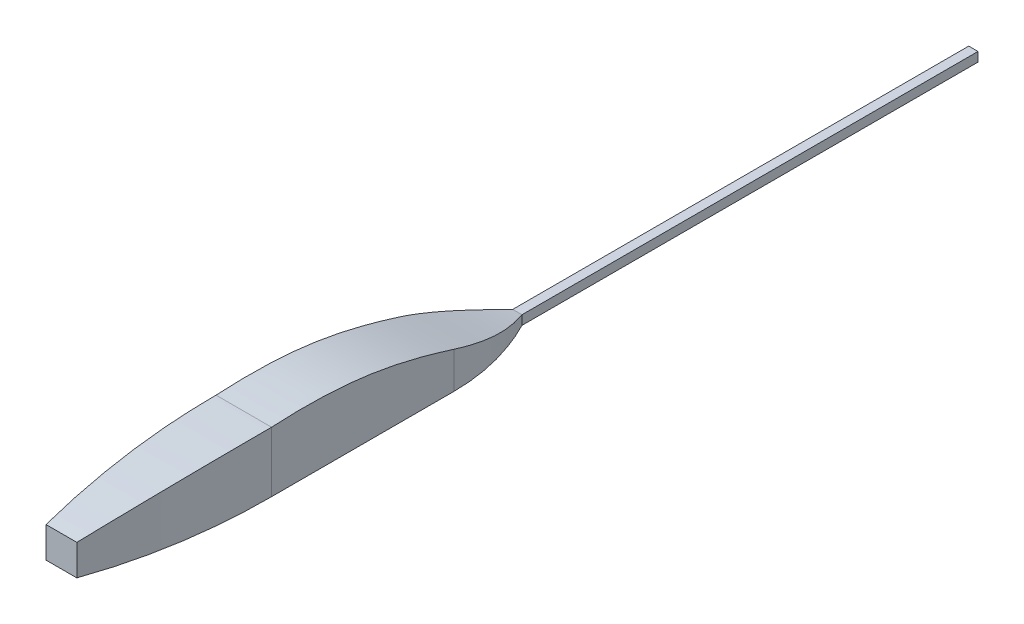
SolidWorks part; units mm, degrees
ref_plane "Front Plane" through (0, 0, 0) normal (0, 0, 1) x (1, 0, 0)
ref_plane "Top Plane" through (0, 0, 0) normal (0, 1, 0) x (1, 0, 0)
ref_plane "Right Plane" through (0, 0, 0) normal (1, 0, 0) x (0, 0, -1)
sketch "Sketch2" plane through (0, 0, 0) normal (0, 0, 1) x (1, 0, 0)
  line L0 (0, 0) -> (14.1421, 14.1421) construction
  line L1 (0, -35.75) -> (0, 35.75) construction
  line L2 (33, 0) -> (-33, 0) construction
  line L3 (-16.6421, 16.6421) -> (16.6421, 16.6421)
  line L4 (-14.1421, -14.1421) -> (14.1421, -14.1421)
  line L5 (-14.1421, -14.1421) -> (-14.1421, 14.1421)
  line L6 (-14.1421, 14.1421) -> (14.1421, 14.1421)
  line L7 (14.1421, -14.1421) -> (14.1421, 14.1421)
  line L8 (-14.1421, -14.1421) -> (14.1421, 14.1421) construction
  line L9 (-14.1421, 14.1421) -> (14.1421, -14.1421) construction
  line L10 (16.6421, -16.6421) -> (16.6421, 16.6421)
  line L11 (-16.6421, -16.6421) -> (16.6421, -16.6421)
  line L12 (-16.6421, -16.6421) -> (-16.6421, 16.6421)
  circle A1 centre (10.253, 10.253) radius 1.5
  circle A2 centre (-10.253, 10.253) radius 1.5
  circle A3 centre (-10.253, -10.253) radius 1.5
  circle A4 centre (10.253, -10.253) radius 1.5
  dimension "D2" = 3
  dimension "D1" = 20
  dimension "D3" = 4
  dimension "D4" = 2.5
sketch "YZ Extrude" plane through (0, 0, 0) normal (1, 0, 0) x (0, 0, -1)
  line L0 (0, 0) -> (197, 0) construction
  line L1 (197, 32.5) -> (197, -32.5) construction
  line L2 (197, 0) -> (394, 0) construction
  line L3 (0, -16.6421) -> (0, 16.6421) construction
  line L4 (394, -32.5) -> (985, -32.5)
  line L5 (98.5, 0) -> (98.5, 32.5)
  line L6 (0, 16.6421) -> (98.5, 32.5) construction
  line L7 (98.5, 32.5) -> (197, 32.5) construction
  line L8 (394, -32.5) -> (394, 32.5) construction
  line L10 (0, -16.6421) -> (98.5, -32.5) construction
  line L11 (98.5, -32.5) -> (197, -32.5) construction
  line L12 (197, -32.5) -> (394, -32.5)
  line L13 (985, -32.5) -> (985, -22.5)
  line L14 (492.5, -22.5) -> (985, -22.5)
  line L15 (492.5, -22.5) -> (492.5, 32.5) construction
  line L16 (297.0882, 29.5681) -> (345.6701, 20.5276)
  line L17 (345.6701, 20.5276) -> (393.2488, 7.178)
  line L19 (0, -16.6421) -> (0, 16.6421)
  line L20 (393.7193, 8.6942) -> (392.7782, 5.6619) construction
  spline S0 degree 2 poles (0, 16.6421) (98.5, 32.5) (197, 32.5) knots 0 0 0 1 1 1
  spline S1 degree 2 poles (0, -16.6421) (98.5, -32.5) (197, -32.5) knots 0 0 0 1 1 1
  spline S2 degree 3 poles (197, 32.5) (230.3593, 34.4809) (280.5151, 33.632) (379.8884, 14.8935) (442.9177, -10.7236) (492.5, -22.5) knots 0 0 0 0 0.331171 0.494445 1 1 1 1
  spline S3 degree 3 poles (393.1263, 7.216) (389.893, 8.2652) (383.442, 10.3586) (370.5028, 14.2229) (354.2993, 18.5842) (334.7723, 23.0541) (315.23, 26.8878) (295.637, 29.894) (276.0085, 32.1248) (259.5715, 32.9273) (246.4033, 32.6498) (236.4892, 31.9272) (226.5265, 30.6379) (218.239, 28.91) (211.5766, 27.0827) (206.5334, 25.2979) (202.2082, 23.3134) (198.4193, 20.8731) (195.0284, 16.8185) (198.3158, 13.4352) (201.7672, 12.0033) (205.9089, 10.9498) (210.8278, 10.279) (217.38, 9.6568) (225.5848, 9.2857) (235.4389, 9.0884) (245.298, 9.1404) (258.4457, 9.1238) (274.8786, 9.1236) (294.5951, 8.9176) (314.3092, 8.7935) (334.0194, 8.5476) (353.7222, 8.1167) (370.134, 7.5901) (383.2607, 7.132) (389.8215, 6.8469) (393.1018, 6.7044) knots 0 0 0 0 0.025305 0.050488 0.10052 0.150191 0.199587 0.24874 0.297716 0.346601 0.371103 0.395726 0.42057 0.445825 0.458702 0.47192 0.485786 0.493461 0.506863 0.516148 0.522766 0.535269 0.547551 0.559786 0.584229 0.608681 0.633151 0.657622 0.706558 0.755482 0.804406 0.85332 0.902221 0.951113 0.975557 1 1 1 1 construction
  point P3 (98.5, 0)
  point P6 (197, 0)
  point P18 (394, 0)
  point P25 (0, 0)
  point P26 (492.5, -22.5)
  point P28 (394, 32.5)
  point P29 (492.5, 32.5)
  point P30 (0, 0)
  point P34 (0, 0)
  point P36 (0, 0)
  point P46 (0, 0)
  point P47 (0, 0)
  point P48 (0, 0)
  point P49 (0, 0)
  point P50 (485.2624, -18.4502)
  point P51 (491.1932, -22.5)
  point P52 (0, 0)
  dimension "D1" = 65
  dimension "D2" = 197
  dimension "D3" = 197
  dimension "D4" = 591
  dimension "D5" = 10
  dimension "D6" = 98.5
sketch "XZ Extrude" plane through (0, 0, 0) normal (0, 1, 0) x (1, 0, 0)
  line L0 (0, 0) -> (0, 197)
  line L1 (0, 197) -> (0, 394)
  line L2 (0, 394) -> (0, 985)
  line L3 (0, 492.5) -> (0, 985) construction
  line L4 (0, 394) -> (0, 985) construction
  line L5 (-16.6421, 0) -> (16.6421, 0)
  line L6 (-16.6421, 0) -> (16.6421, 0) construction
  line L7 (-30, 98.5) -> (30, 98.5) construction
  line L8 (-30, 197) -> (30, 197) construction
  line L9 (-30, 394) -> (30, 394) construction
  line L10 (-30, 443.25) -> (30, 443.25) construction
  line L11 (-5, 985) -> (5, 985)
  line L12 (30, 197) -> (30, 98.5) construction
  line L13 (30, 98.5) -> (16.6421, 0) construction
  line L14 (30, 197) -> (30, 394)
  line L15 (5, 985) -> (5, 394) construction
  line L16 (-5, 985) -> (-5, 394) construction
  line L17 (30, 394) -> (30, 443.25) construction
  line L18 (30, 443.25) -> (5, 492.5) construction
  line L19 (5, 492.5) -> (5, 985)
  line L20 (-30, 394) -> (-30, 443.25) construction
  line L21 (-30, 443.25) -> (-5, 492.5) construction
  line L22 (-5, 492.5) -> (-5, 985)
  line L23 (-30, 197) -> (-30, 98.5) construction
  line L24 (-30, 98.5) -> (-16.6421, 0) construction
  line L25 (-30, 197) -> (-30, 394)
  line L27 (0, 492.5) -> (0, 394) construction
  line L28 (0, 492.5) -> (0, 394) construction
  line L29 (-5, 443.25) -> (5, 443.25)
  spline S0 degree 2 poles (30, 197) (30, 98.5) (16.6421, 0) knots 0 0 0 1 1 1
  spline S1 degree 2 poles (30, 394) (30, 443.25) (5, 492.5) knots 0 0 0 1 1 1
  spline S2 degree 2 poles (-30, 394) (-30, 443.25) (-5, 492.5) knots 0 0 0 1 1 1
  spline S3 degree 2 poles (-30, 197) (-30, 98.5) (-16.6421, 0) knots 0 0 0 1 1 1
  point P4 (5, 492.5)
  point P16 (0, 0)
  point P20 (0, 98.5)
  point P23 (0, 197)
  point P25 (0, 394)
  point P29 (0, 443.25)
  point P32 (0, 985)
  point P34 (0, 492.5)
  point P45 (0, 443.25)
  point P48 (0, 443.25)
  point P49 (0, 443.25)
  dimension "D1" = 60
  dimension "D2" = 60
  dimension "D3" = 60
  dimension "D4" = 10
  dimension "D5" = 98.5
  dimension "D6" = 591
extrude "Top Down" add sketch "XZ Extrude" along normal blind 50 and the other way blind 50 contours S2 L22 L11 L19 S1 L14 S0 L5 S3 L25
extrude "Cut-Extrude2" cut sketch "YZ Extrude" along normal up to surface (30 mm away) and the other way up to surface (30 mm away) flip side to cut contours S0 S2 L14 L13 L4 L12 S1 L19 up to face at (30, 0, -295.5) other way up to face at (-30, 0, -295.5)
